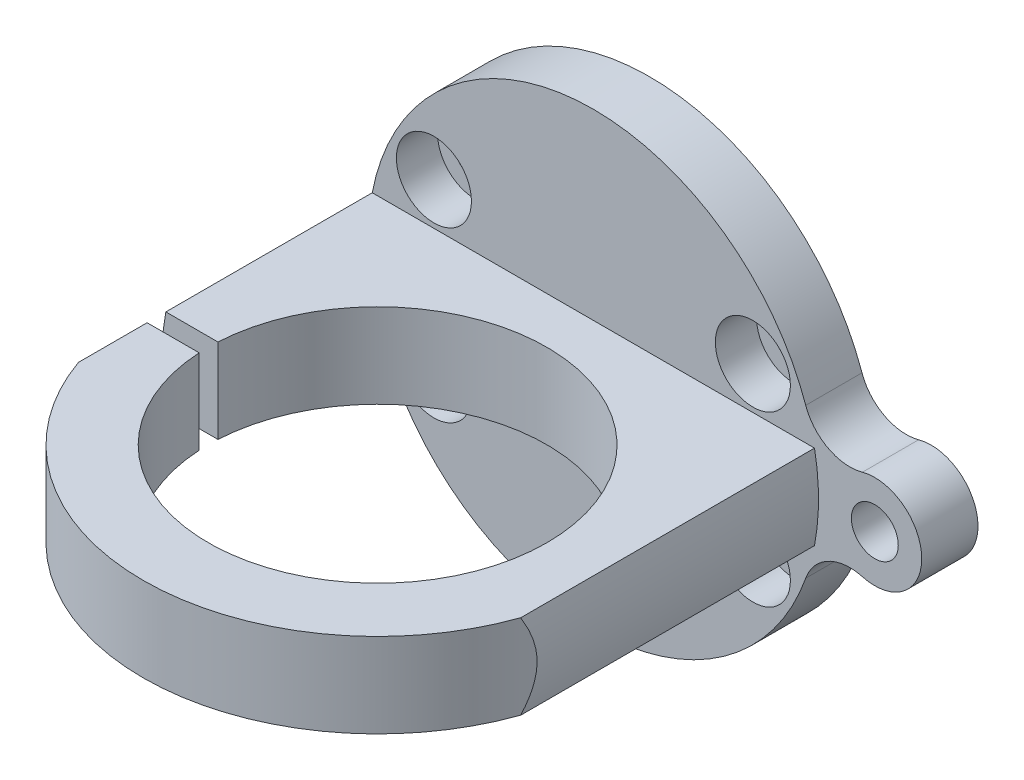
SolidWorks part; units mm, degrees
material "Alumina"
ref_plane "Plan de face" through (0, 0, 0) normal (0, 0, 1) x (1, 0, 0)
ref_plane "Plan de dessus" through (0, 0, 0) normal (0, 1, 0) x (1, 0, 0)
ref_plane "Plan de droite" through (0, 0, 0) normal (1, 0, 0) x (0, 0, -1)
sketch "Sketch1" plane through (0, 0, 0) normal (0, 0, 1) x (1, 0, 0)
  circle A0 centre (0, 0) radius 24
  dimension "D1" = 48
extrude "Boss-Extrude1" add sketch "Sketch1" against normal blind 6
sketch "Sketch2" plane through (0, 0, 0) normal (0, 1, 0) x (1, 0, 0)
  line L0 (24, 6) -> (-24, 6) construction
  line L19 (-28.8436, -24) -> (-14.1769, -24)
  line L28 (-28.8436, -24) -> (-28.8436, -22)
  line L29 (-25, 6) -> (25, 6)
  line L30 (-25, 6) -> (-25, -23)
  line L32 (25, 6) -> (25, -23)
  line L33 (-28.8436, -22) -> (-14.1769, -22)
  line L34 (-14.1769, -24) -> (-14.1769, -22)
  line L35 (-28.8436, -24) -> (-14.1769, -22) construction
  line L36 (-28.8436, -22) -> (-14.1769, -24) construction
  circle A1 centre (0, -23) radius 18.05
  arc A3 (-25, -23) -> (25, -23) centre (0, -23) ccw
  point P10 (-21.5103, -23)
  dimension "D1" = 2
  dimension "D4" = 36.1
  dimension "D2" = 23
  dimension "D3" = 50
extrude "Boss-Extrude2" add sketch "Sketch2" against normal blind 4.5 and the other way blind 4.5 contours L30 A3 L32 L29 A1 region at (-21.5011, 0, 24.7359)
hole_wizard "Chambrage pour vis à tête hexagonale M42" positions "Sketch3" profile "Sketch4" counterbore size "M4" standard "ISO" end condition through all
sketch "Sketch3" plane through (0, 0, 0) normal (0, 0, 1) x (1, 0, 0)
  line L6 (-17, -9) -> (17, -9) construction
  line L7 (-17, -9) -> (-17, 9) construction
  line L8 (-17, 9) -> (17, 9) construction
  line L9 (17, -9) -> (17, 9) construction
  line L10 (-17, -9) -> (17, 9) construction
  line L11 (-17, 9) -> (17, -9) construction
  point P15 (17, 9)
  point P126 (-17, -9)
  point P127 (-17, 9)
  point P128 (17, -9)
  dimension "D1" = 18
  dimension "D2" = 34
sketch "Sketch4" plane through (17, 9, 0) normal (1, 0, 0) x (0, -1, 0)
  line L0 (0, 0) -> (0, 6)
  line L1 (0, 6) -> (2.25, 6)
  line L3 (2.25, 6) -> (2.25, 4.4)
  line L4 (2.25, 4.4) -> (4, 4.4)
  line L5 (4, 4.4) -> (4, 0)
  line L7 (4, 0) -> (0, 0)
  line L11 (0, -6.35) -> (0, 107.95) construction
  dimension "Thru Hole Dia." = 4.5
  dimension "Thru Hole Depth" = 6
  dimension "C'Bore Dia." = 8
  dimension "C'Bore Depth" = 4.4
ref_plane "Plan1" through (0, 0, 44) normal (0, 0, -1) x (-1, 0, 0)
hole_wizard "Chambrage pour vis à tête hexagonale M31" positions "Esquisse1" profile "Esquisse2" counterbore size "M3" standard "ISO"
sketch "Esquisse1" plane through (0, 0, 44) normal (0, 0, -1) x (-1, 0, 0)
  point P0 (21.5, 0)
  dimension "D1" = 21.5
sketch "Esquisse2" plane through (-21.5, 0, 44) normal (1, 0, 0) x (0, -1, 0)
  line L0 (0, 0) -> (0, 21)
  line L1 (0, 21) -> (1.7, 21)
  line L2 (1.7, 21) -> (1.7, 15.4)
  line L3 (1.7, 15.4) -> (3.25, 15.4)
  line L4 (3.25, 15.4) -> (3.25, 0)
  line L5 (3.25, 0) -> (0, 0)
  line L10 (0, 21) -> (-1.7, 21) construction
  line L11 (0, -6.35) -> (0, 107.95) construction
  dimension "Diamètre du perçage" = 3.4
  dimension "Profondeur du perçage" = 21
  dimension "Diamètre du chambrage" = 6.5
  dimension "Profondeur du chambrage" = 15.4
  dimension "Angle de pointe" = 180
hole_wizard "Trou pour taraudage pour trou taraudé M31" positions "Esquisse3" profile "Esquisse4" hole size "M3" standard "ISO"
sketch "Esquisse3" plane through (0, 0, 22) normal (0, 0, 1) x (1, 0, 0)
  point P0 (-21.5, 0)
sketch "Esquisse4" plane through (-21.5, 0, 22) normal (1, 0, 0) x (0, -1, 0)
  line L0 (0, 0) -> (0, 10.7511)
  line L1 (0, 10.7511) -> (1.25, 10)
  line L2 (1.25, 10) -> (1.25, 0)
  line L5 (1.25, 0) -> (0, 0)
  line L10 (0, 10.7511) -> (-1.25, 10) construction
  line L11 (0, -6.35) -> (0, 107.95) construction
  dimension "Diamètre du perçage" = 2.5
  dimension "Profondeur du perçage" = 10
  dimension "Angle de pointe" = 118
sketch "Esquisse8" plane through (0, 0, 0) normal (0, 0, 1) x (1, 0, 0)
  circle A0 centre (0, 0) radius 24
  dimension "D1" = 48
extrude "Enlèv. mat.-Extru.3" cut sketch "Esquisse8" against normal through all both and the other way through all flip side to cut
sketch "Esquisse9" plane through (0, 0, -6) normal (0, 0, -1) x (-1, 0, 0)
  arc A0 (-28.675, 4.8212) -> (-28.675, -4.8212) centre (-30, 0) ccw
  arc A1 (-22.6345, -7.98) -> (-28.675, -4.8212) centre (-27.35, -9.6425) ccw
  circle A2 centre (0, 0) radius 24 construction
  arc A4 (-22.6345, 7.98) -> (-28.675, 4.8212) centre (-27.35, 9.6425) cw
  circle A5 centre (0, 0) radius 24
  arc A6 (-22.6345, 7.98) -> (-22.6345, -7.98) centre (0, 0) ccw
  dimension "D1" = 10
  dimension "D2" = 30
  dimension "D4" = 5
  dimension "D3" = 0
extrude "Boss.-Extru.1" add sketch "Esquisse9" against normal blind 6
hole_wizard "Trou pour taraudage pour trou taraudé M62" positions "Esquisse10" profile "Esquisse11" hole size "M6" standard "ISO" end condition through all
sketch "Esquisse10" plane through (0, 0, 0) normal (0, 0, 1) x (1, 0, 0)
  point P0 (30, 0)
sketch "Esquisse11" plane through (30, 0, 0) normal (1, 0, 0) x (0, -1, 0)
  line L0 (0, 0) -> (0, 6)
  line L1 (0, 6) -> (2.5, 6)
  line L2 (2.5, 6) -> (2.5, 0)
  line L5 (2.5, 0) -> (0, 0)
  line L11 (0, -6.35) -> (0, 107.95) construction
  dimension "Diamètre du perçage jusqu'au prochain" = 5
  dimension "Profondeur du perçage jusqu'au prochain" = 6
